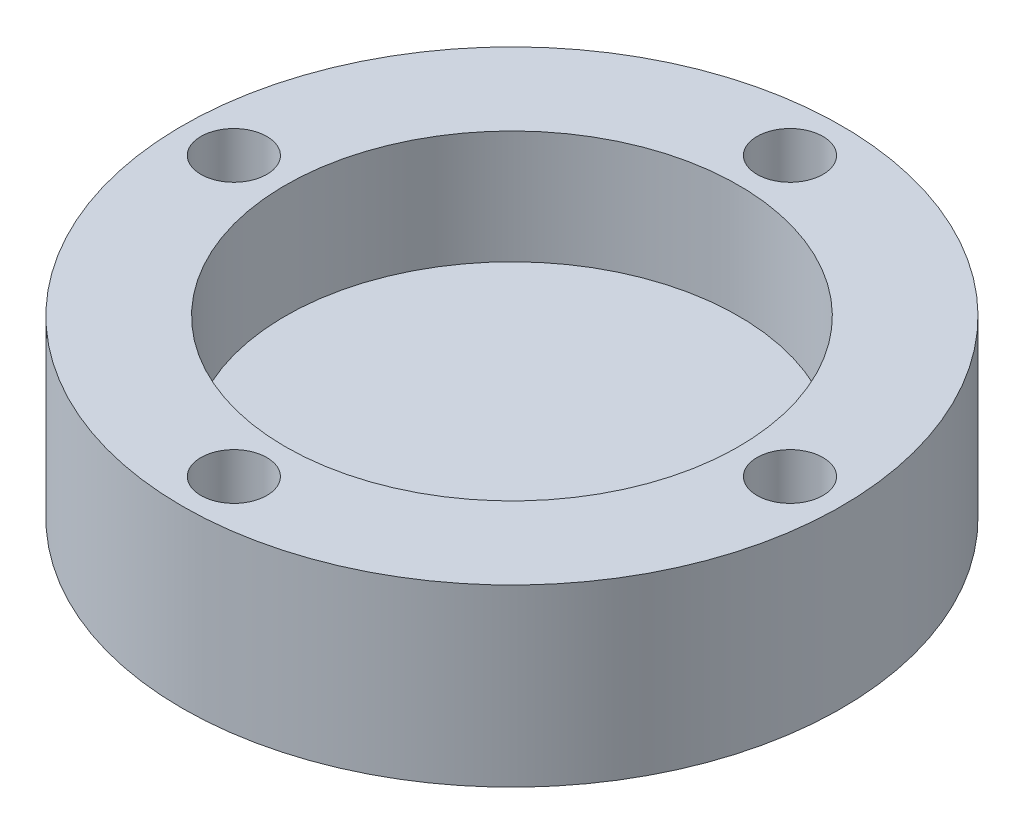
SolidWorks part; units mm, degrees
ref_plane "Front Plane" through (0, 0, 0) normal (0, 0, 1) x (1, 0, 0)
ref_plane "Top Plane" through (0, 0, 0) normal (0, 1, 0) x (1, 0, 0)
ref_plane "Right Plane" through (0, 0, 0) normal (1, 0, 0) x (0, 0, -1)
ref_axis "Axe1" through (0, 8.4, 0) along (0, -1, 0)
sketch "Esquisse1" plane through (0, 0, 0) normal (0, 0, 1) x (1, 0, 0)
  line L0 (11, 8.5) -> (11, 3)
  line L1 (11, 3) -> (0, 3)
  line L2 (0, 3) -> (0, 0)
  line L3 (0, 0) -> (16, 0)
  line L4 (16, 0) -> (16, 8.5)
  line L5 (11, 8.5) -> (16, 8.5)
  dimension "D1" = 5.5
  dimension "D2" = 3
  dimension "D3" = 11
  dimension "D4" = 5
revolve "MainRevolution" add sketch "Esquisse1" angle 360 about axis through (0, 8.4, 0) along (0, -1, 0)
sketch "Esquisse2" plane through (0, 8.5, 0) normal (0, 1, 0) x (1, 0, 0)
  circle A0 centre (13.5, 0) radius 1.6
  dimension "D1" = 3.2
  dimension "D2" = 13.5
extrude "FixingHole" cut sketch "Esquisse2" against normal through all
pattern_circular "FixingHoleRepetition" count 4 every 90 about axis through (0, 8.4, 0) along (0, -1, 0) of "FixingHole"
